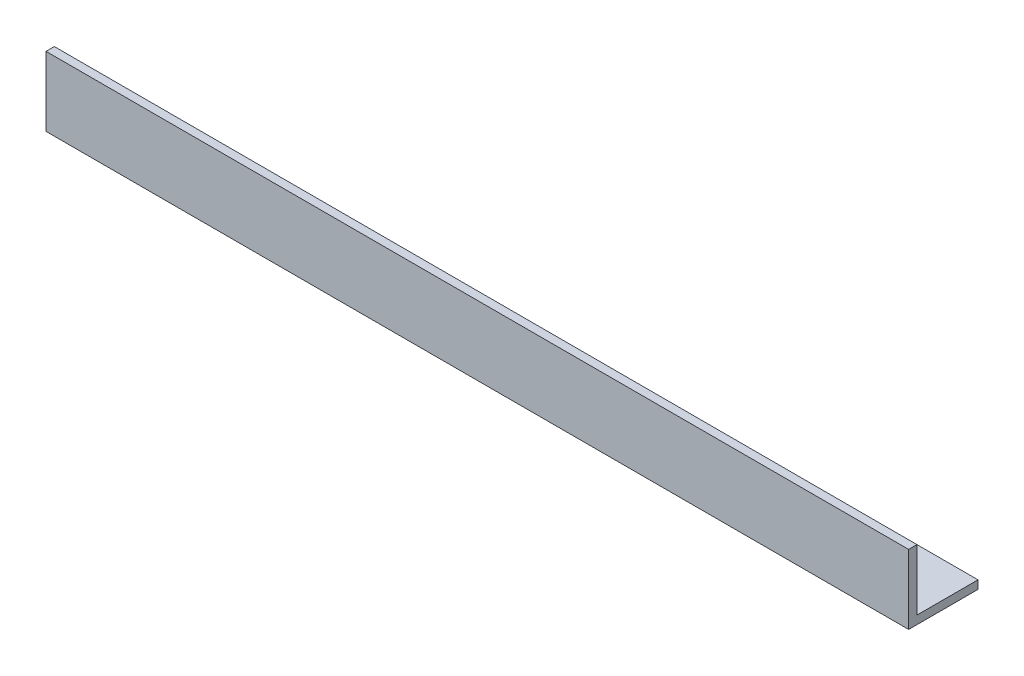
SolidWorks part; units mm, degrees
ref_plane "Спереди" through (0, 0, 0) normal (0, 0, 1) x (1, 0, 0)
ref_plane "Сверху" through (0, 0, 0) normal (0, 1, 0) x (1, 0, 0)
ref_plane "Справа" through (0, 0, 0) normal (1, 0, 0) x (0, 0, -1)
sketch "Эскиз1" plane through (0, 0, 0) normal (1, 0, 0) x (0, 0, -1)
  line L0 (0, 0) -> (50, 0)
  line L5 (0, 50) -> (0, 0)
extrude "Вытянуть-Тонкостенный2" add sketch "Эскиз1" along normal blind 622 thin thin type one direction reverse wall 6
